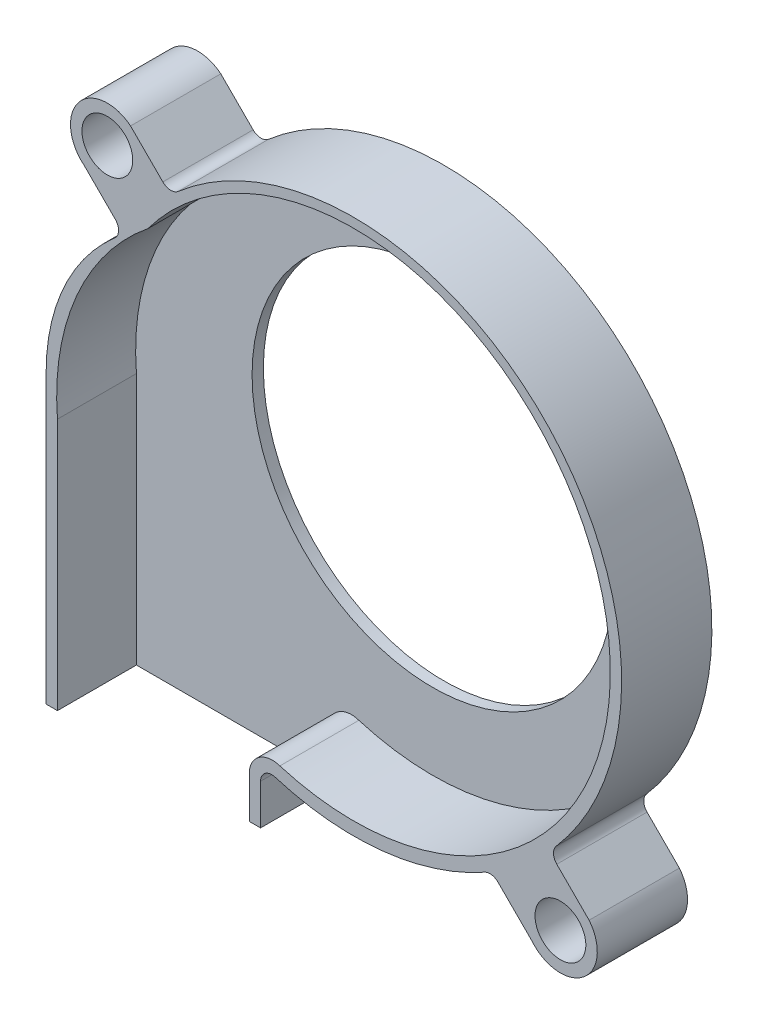
SolidWorks part; units mm, degrees
ref_plane "Płaszczyzna przednia" through (0, 0, 0) normal (0, 0, 1) x (1, 0, 0)
ref_plane "Płaszczyzna górna" through (0, 0, 0) normal (0, 1, 0) x (1, 0, 0)
ref_plane "Płaszczyzna prawa" through (0, 0, 0) normal (1, 0, 0) x (0, 0, -1)
sketch "Sketch1" plane through (0, 0, 0) normal (0, 0, 1) x (1, 0, 0)
  line L2 (51.0132, 0.0687) -> (51.0132, 51.0687) construction
  line L16 (44.4446, 2.0412) -> (1.9857, 44.5001) construction
  line L17 (49.0408, 6.6374) -> (6.5819, 49.0963) construction
  line L18 (51, 51) -> (0, 0) construction
  line L19 (51, 0) -> (0, 51) construction
  line L20 (0, 0) -> (0, 51) construction
  line L21 (51, 51) -> (0, 51) construction
  line L22 (51, 0) -> (0, 0) construction
  line L23 (47.4487, 25.5687) -> (3.5778, 25.5687) construction
  line L24 (11.0133, 44.5829) -> (7.4777, 48.1185)
  line L25 (6.9033, 39.5005) -> (3.3678, 43.036)
  line L26 (39.5005, 6.9033) -> (43.036, 3.3678)
  line L27 (44.5829, 11.0133) -> (48.1185, 7.4777)
  line L28 (19, 0) -> (19, 4.9789)
  line L29 (0, 0) -> (19, 0)
  line L30 (0, 0) -> (0, 25.5)
  arc A6 (39.5005, 6.9033) -> (19, 4.9789) centre (27.25, 27.25) cw
  arc A7 (11.0133, 44.5829) -> (44.5829, 11.0133) centre (27.25, 27.25) cw
  arc A8 (7.4777, 48.1185) -> (3.3678, 43.036) centre (5.4227, 45.5773) ccw
  arc A9 (48.1185, 7.4777) -> (43.036, 3.3678) centre (45.5773, 5.4227) cw
  arc A10 (0, 25.5) -> (6.8957, 39.4878) centre (17.6349, 25.5) cw
  arc A11 (6.8957, 39.4878) -> (6.9033, 39.5005) centre (27.25, 27.25) cw
  point P1 (0, 0)
  point P3 (0, 0)
  point P4 (0, 0)
  point P78 (27.8113, 27.8668)
  point P79 (25.5132, 25.5687)
  point P80 (25.5132, 25.5687)
extrude "Boss-Extrude1" add sketch "Sketch1" along normal blind 8
fillet "Fillet1" radius 1 4 edges at (6.8995, 39.4942, 0) (6.8957, 39.4878, 4) (6.9033, 39.5005, 4) (6.8995, 39.4942, 8)
fillet "Fillet2" radius 1 3 edges at (39.5005, 6.9033, 4) (44.5829, 11.0133, 4) (11.0133, 44.5829, 4)
fillet "Fillet3" radius 1 1 edges at (19, 4.9789, 4)
sketch "Sketch2" plane through (0, 0, 8) normal (0, 0, 1) x (1, 0, 0)
  line L3 (0, 25.5) -> (0, 0) construction
  line L4 (0, 0) -> (19, 0) construction
  line L7 (1, 0) -> (1, 22.3742)
  line L8 (18, 0) -> (1, 0)
  line L9 (18, 0) -> (18, 3.5465)
  arc A1 (18, 3.5465) -> (20.7133, 5.616) centre (20.0532, 3.6681) cw
  arc A4 (1, 22.3742) -> (9.0077, 41.0001) centre (22.6397, 24.1051) cw
  arc A6 (9.0077, 41.0001) -> (20.7133, 5.616) centre (27.25, 27.4067) cw
  point P0 (0, 0)
  dimension "D1" = 1
extrude "Cut-Extrude1" cut sketch "Sketch2" against normal blind 7
sketch "Sketch3" plane through (0, 0, 1) normal (0, 0, 1) x (1, 0, 0)
  circle A0 centre (27.25, 27.4067) radius 16
  arc A2 (20.7133, 5.616) -> (9.0077, 41.0001) centre (27.25, 27.4067) ccw construction
  dimension "D1" = 32
extrude "Cut-Extrude2" cut sketch "Sketch3" against normal blind 7
hole_wizard "Ø4.0mm Dowel Hole1" positions "Sketch6" profile "Sketch5" hole size "Ø4.0" standard "ANSI Metric" end condition through all
sketch "Sketch6" plane through (0, 0, 0) normal (0, 0, -1) x (-1, 0, 0)
  line L2 (-3.3678, 43.036) -> (-6.1252, 40.2786) construction
  line L3 (-48.1185, 7.4777) -> (-45.2539, 10.3423) construction
  arc A8 (-3.3678, 43.036) -> (-7.4777, 48.1185) centre (-5.4227, 45.5773) ccw construction
  arc A9 (-48.1185, 7.4777) -> (-43.036, 3.3678) centre (-45.5773, 5.4227) ccw construction
  point P0 (-45.5773, 5.4227)
  point P2 (-5.4227, 45.5773)
  point P29 (-8.6573, 45.4018)
  point P32 (0, 0)
  point P42 (-6.2881, 44.7119)
  point P46 (-4.9672, 46.0328)
  point P50 (-43.6354, 6.5712)
  dimension "D1" = 3.25
  dimension "D2" = 3.25
  dimension "D3" = 0
  dimension "D4" = 0
sketch "Sketch5" plane through (45.5773, 5.4227, 0) normal (1, 0, 0) x (0, 1, 0)
  line L0 (0, 0) -> (0, 8)
  line L1 (0, 8) -> (2.25, 8)
  line L2 (2.25, 8) -> (2.25, 0)
  line L5 (2.25, 0) -> (0, 0)
  line L11 (0, -6.35) -> (0, 107.95) construction
  dimension "Thru Hole Dia." = 4.5
  dimension "Thru Hole Depth" = 8
